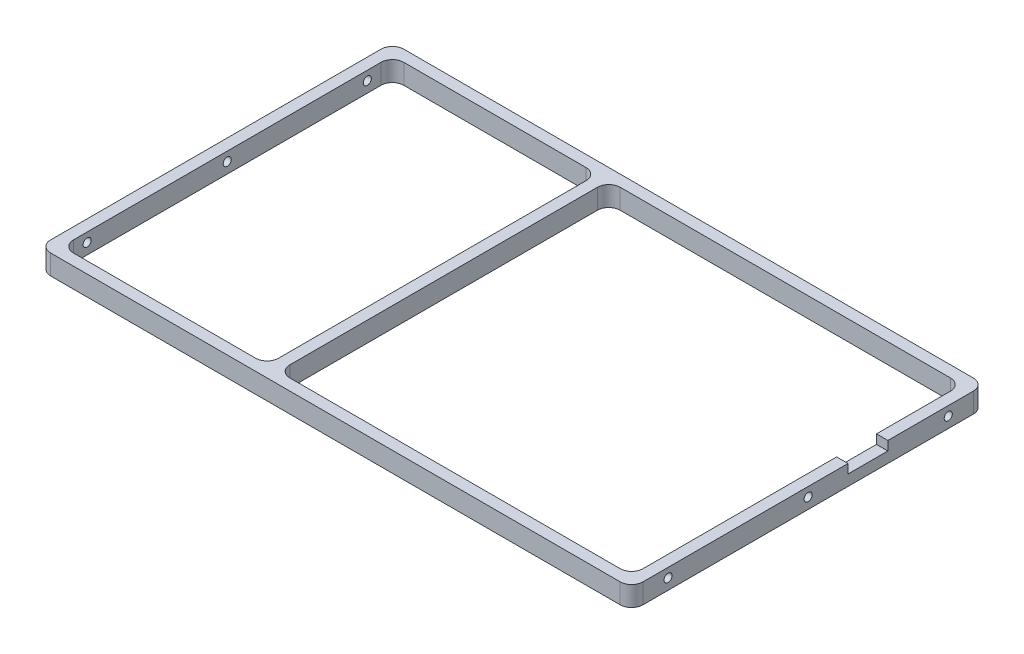
SolidWorks part; units mm, degrees
material "Delrin 2700 NC010, Low Viscosity Acetal Copolymer (SS)"
ref_plane "Front Plane" through (0, 0, 0) normal (0, 0, 1) x (1, 0, 0)
ref_plane "Top Plane" through (0, 0, 0) normal (0, 1, 0) x (1, 0, 0)
ref_plane "Right Plane" through (0, 0, 0) normal (1, 0, 0) x (0, 0, -1)
sketch "Sketch1" plane through (0, 0, 0) normal (0, 1, 0) x (1, 0, 0)
  line L1 (-165.1, -98.425) -> (165.1, -98.425)
  line L2 (-165.1, -98.425) -> (-165.1, 98.425)
  line L3 (-165.1, 98.425) -> (165.1, 98.425)
  line L4 (165.1, -98.425) -> (165.1, 98.425)
  line L5 (-165.1, -98.425) -> (165.1, 98.425) construction
  line L6 (-165.1, 98.425) -> (165.1, -98.425) construction
  point P0 (0, 0)
  dimension "D1" = 330.2
  dimension "D2" = 196.85
extrude "Boss-Extrude1" add sketch "Sketch1" along normal blind 11.1125
sketch "Sketch3" plane through (0, 11.1125, 0) normal (0, 1, 0) x (1, 0, 0)
  line L0 (-165.1, 98.425) -> (-165.1, -98.425) construction
  line L1 (-158.75, -92.075) -> (158.75, -92.075)
  line L2 (-158.75, -92.075) -> (-158.75, 92.075)
  line L3 (-158.75, 92.075) -> (158.75, 92.075)
  line L4 (158.75, -92.075) -> (158.75, 92.075)
  line L5 (-158.75, -92.075) -> (158.75, 92.075) construction
  line L6 (-158.75, 92.075) -> (158.75, -92.075) construction
  line L7 (165.1, 98.425) -> (-165.1, 98.425) construction
  point P0 (0, 0)
  dimension "D1" = 6.35
  dimension "D2" = 6.35
extrude "Cut-Extrude1" cut sketch "Sketch3" against normal through all
fillet "Fillet1" radius 6.35 8 edges at (158.75, 5.5562, -92.075) (165.1, 5.5562, -98.425) (158.75, 5.5562, 92.075) (165.1, 5.5562, 98.425) (-158.75, 5.5562, 92.075) (-165.1, 5.5562, 98.425) (-165.1, 5.5562, -98.425) (-158.75, 5.5562, -92.075)
sketch "Sketch4" plane through (0, 0, -92.075) normal (0, 0, 1) x (1, 0, 0)
  line L0 (152.4, 11.1125) -> (-152.4, 11.1125) construction
  line L1 (-44.45, 11.1125) -> (-38.1, 11.1125)
  line L2 (-44.45, 11.1125) -> (-44.45, 0)
  line L3 (-44.45, 0) -> (-38.1, 0)
  line L4 (-38.1, 11.1125) -> (-38.1, 0)
  line L5 (152.4, 0) -> (-152.4, 0) construction
  line L6 (-165.1, 11.1125) -> (-165.1, 0) construction
  dimension "D1" = 6.35
  dimension "D2" = 127
extrude "Boss-Extrude2" add sketch "Sketch4" along normal up to surface (184.15 mm away) up to face at (0, 5.5562, 92.075)
fillet "Fillet2" radius 6.35 4 edges at (-44.45, 5.5562, 92.075) (-38.1, 5.5562, 92.075) (-38.1, 5.5562, -92.075) (-44.45, 5.5562, -92.075)
hole_wizard "#8 Clearance Hole1" positions "Sketch7" profile "Sketch6" hole size "#8" standard "Ansi Inch" end condition up to next
sketch "Sketch7" plane through (-165.1, 0, 0) normal (-1, 0, 0) x (0, 0, 1)
  line L0 (-98.425, 0) -> (-98.425, 11.1125) construction
  line L1 (98.425, 11.1125) -> (98.425, 0) construction
  line L2 (-92.075, 11.1125) -> (92.075, 11.1125) construction
  point P0 (-78.105, 6.0325)
  point P1 (0, 6.0325)
  point P3 (78.105, 6.0325)
  dimension "D1" = 20.32
  dimension "D2" = 20.32
  dimension "D3" = 5.08
sketch "Sketch6" plane through (-165.1, 6.0325, -78.105) normal (0, 1, 0) x (0, 0, 1)
  line L0 (0, 0) -> (0, 127)
  line L1 (0, 127) -> (2.2479, 127)
  line L2 (2.2479, 127) -> (2.2479, 0)
  line L5 (2.2479, 0) -> (0, 0)
  line L11 (0, -6.35) -> (0, 107.95) construction
  dimension "Thru Hole Dia." = 4.4958
  dimension "Thru Hole Depth" = 127
mirror "Mirror1" about plane through (0, 0, 0) normal (1, 0, 0) of "#8 Clearance Hole1"
hole_wizard "#4-40 Tapped Hole1" positions "Sketch10" profile "Sketch9" tap size "#4-40" standard "Ansi Inch"
sketch "Sketch10" plane through (0, 0, 0) normal (0, -1, 0) x (1, 0, 0)
  line L0 (-170.1636, 94.615) -> (165.1, 94.615) construction
  line L2 (-158.75, 98.425) -> (158.75, 98.425) construction
  line L3 (-165.1, -92.075) -> (-165.1, 92.075) construction
  point P0 (-158.75, 94.615)
  point P1 (-101.6, 94.615)
  point P3 (-41.275, 94.615)
  point P5 (28.575, 94.615)
  point P7 (88.9, 94.615)
  point P9 (158.75, 94.615)
  dimension "D1" = 3.81
  dimension "D2" = 6.35
  dimension "D3" = 57.15
  dimension "D4" = 117.475
  dimension "D5" = 200.025
  dimension "D6" = 69.85
  dimension "D7" = 69.85
sketch "Sketch9" plane through (-158.75, 0, 94.615) normal (1, 0, 0) x (0, 0, -1)
  line L0 (0, 0) -> (0, 8.2992)
  line L1 (0, 8.2992) -> (1.1303, 7.62)
  line L2 (1.1303, 7.62) -> (1.1303, 0)
  line L5 (1.1303, 0) -> (0, 0)
  line L10 (0, 8.2992) -> (-1.1303, 7.62) construction
  line L11 (0, -6.35) -> (0, 107.95) construction
  dimension "Tap Drill Dia." = 2.2606
  dimension "Tap Drill Depth" = 7.62
  dimension "Drill Angle" = 118
cosmetic thread "Hole Thread1"
cosmetic thread "Hole Thread2"
cosmetic thread "Hole Thread3"
cosmetic thread "Hole Thread4"
cosmetic thread "Hole Thread5"
cosmetic thread "Hole Thread6"
mirror "Mirror2" about plane through (0, 0, 0) normal (0, 0, 1) of "#4-40 Tapped Hole1"
hole_wizard "#4-40 Tapped Hole2" positions "Sketch12" profile "Sketch11" tap size "#4-40" standard "Ansi Inch"
sketch "Sketch12" plane through (0, 0, 0) normal (0, -1, 0) x (1, 0, 0)
  line L0 (-165.1, -92.075) -> (-165.1, 92.075) construction
  line L1 (-158.75, 98.425) -> (158.75, 98.425) construction
  line L2 (158.75, -98.425) -> (-158.75, -98.425) construction
  point P0 (-161.29, 47.625)
  point P3 (-161.29, -47.625)
  dimension "D1" = 3.81
  dimension "D2" = 50.8
  dimension "D3" = 50.8
sketch "Sketch11" plane through (-161.29, 0, 47.625) normal (1, 0, 0) x (0, 0, -1)
  line L0 (0, 0) -> (0, 8.2992)
  line L1 (0, 8.2992) -> (1.1303, 7.62)
  line L2 (1.1303, 7.62) -> (1.1303, 0)
  line L5 (1.1303, 0) -> (0, 0)
  line L10 (0, 8.2992) -> (-1.1303, 7.62) construction
  line L11 (0, -6.35) -> (0, 107.95) construction
  dimension "Tap Drill Dia." = 2.2606
  dimension "Tap Drill Depth" = 7.62
  dimension "Drill Angle" = 118
cosmetic thread "Hole Thread7"
cosmetic thread "Hole Thread9"
pattern_linear "LPattern1" count 2 spacing 120.015 along (1, 0, 0) of "#4-40 Tapped Hole2"
mirror "Mirror3" about plane through (0, 0, 0) normal (1, 0, 0) of "#4-40 Tapped Hole2"
sketch "Sketch13" plane through (165.1, 0, 0) normal (1, 0, 0) x (0, 0, -1)
  line L1 (-92.075, 11.1125) -> (92.075, 11.1125) construction
  line L2 (22.225, 11.1125) -> (44.45, 11.1125)
  line L3 (22.225, 11.1125) -> (22.225, 6.0325)
  line L4 (22.225, 6.0325) -> (44.45, 6.0325)
  line L5 (44.45, 11.1125) -> (44.45, 6.0325)
  line L6 (98.425, 11.1125) -> (98.425, 0) construction
  dimension "D1" = 5.08
  dimension "D2" = 53.975
  dimension "D3" = 22.225
extrude "Cut-Extrude2" cut sketch "Sketch13" against normal up to next
